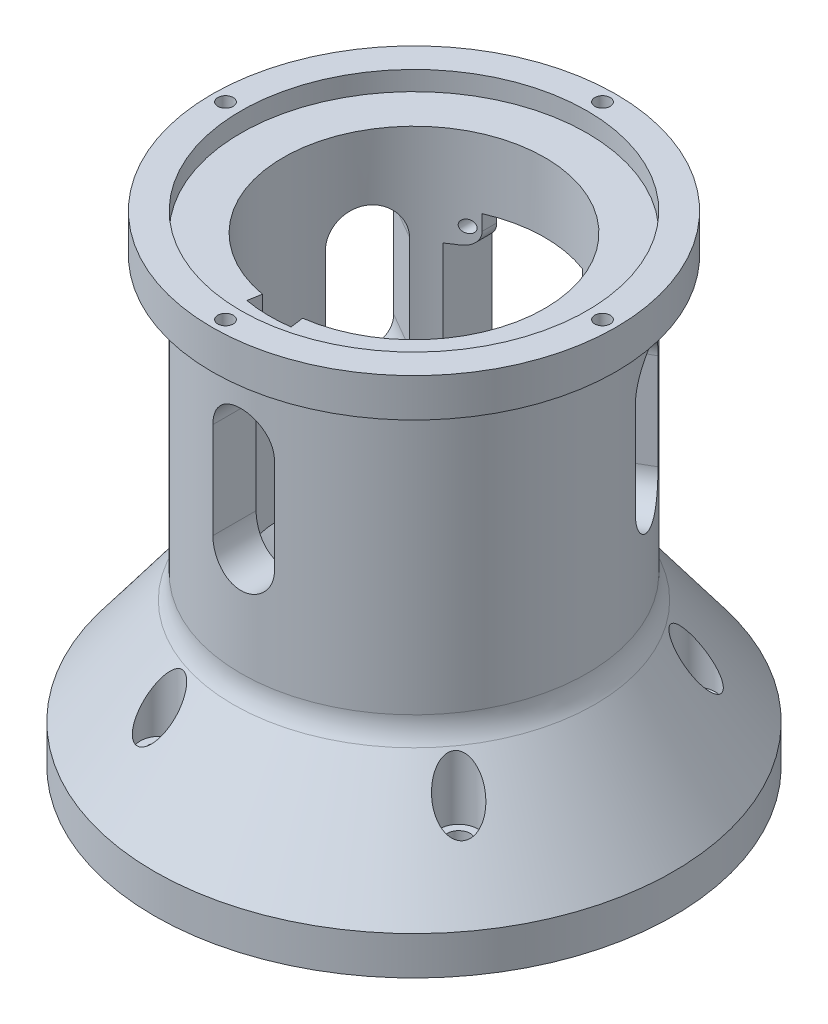
SolidWorks part; units mm, degrees
ref_plane "Front Plane" through (0, 0, 0) normal (0, 0, 1) x (1, 0, 0)
ref_plane "Top Plane" through (0, 0, 0) normal (0, 1, 0) x (1, 0, 0)
ref_plane "Right Plane" through (0, 0, 0) normal (1, 0, 0) x (0, 0, -1)
sketch "Sketch1" plane through (0, 0, 0) normal (0, 1, 0) x (1, 0, 0)
  circle A0 centre (0, 0) radius 67.5
  dimension "D1" = 135
ref_plane "Plane1" through (0, 30, 0) normal (0, 1, 0) x (1, 0, 0)
sketch "Sketch2" plane through (0, 30, 0) normal (0, 1, 0) x (1, 0, 0)
  circle A0 centre (0, 0) radius 45
  dimension "D1" = 90
loft "Loft1" add profiles "Sketch1", "Sketch2" connector at (0, 0, 67.5) connector at (0, 30, 45)
sketch "Sketch4" plane through (0, 30, 0) normal (0, 1, 0) x (1, 0, 0)
  circle A0 centre (0, 0) radius 52.5 construction
  circle A1 centre (-52.5, 0) radius 3
  circle A2 centre (-16.2234, 49.9305) radius 3
  circle A3 centre (42.4734, 30.8587) radius 3
  circle A4 centre (42.4734, -30.8587) radius 3
  circle A5 centre (-16.2234, -49.9305) radius 3
  point P15 (0, 0)
  dimension "D1" = 105
  dimension "D2" = 6
  dimension "D3" = 5
extrude "Cut-Extrude2" cut sketch "Sketch4" against normal through all
sketch "Sketch5" plane through (0, 30, 0) normal (0, 1, 0) x (1, 0, 0)
  circle A0 centre (-52.5, 0) radius 3 construction
  circle A1 centre (-52.5, 0) radius 3
  circle A2 centre (-52.5, 0) radius 5
  circle A3 centre (-16.2234, 49.9305) radius 5
  circle A4 centre (42.4734, 30.8587) radius 5
  circle A5 centre (42.4734, -30.8587) radius 5
  circle A6 centre (-16.2234, -49.9305) radius 5
  point P14 (0, 0)
  dimension "D1" = 10
  dimension "D3" = 52.5
  dimension "D2" = 5
extrude "Cut-Extrude3" cut sketch "Sketch5" against normal blind 20
sketch "Sketch6" plane through (0, 30, 0) normal (0, 1, 0) x (1, 0, 0)
  circle A1 centre (0, 0) radius 45
  circle A2 centre (0, 0) radius 45
  dimension "D1" = 0
extrude "Boss-Extrude1" add sketch "Sketch6" along normal blind 80
fillet "Fillet1" radius 10 1 edges at (0, 30, 45)
sketch "Sketch11" plane through (17.444, 57.5446, 0) normal (0, 0, 1) x (1, 0, 0)
  line L0 (-17.444, 52.4554) -> (-51.444, 52.4554)
  line L1 (27.556, 52.4554) -> (-62.444, 52.4554) construction
  line L2 (-51.444, 52.4554) -> (-51.444, -28.5446)
  line L5 (-51.444, -28.5446) -> (-40.444, -38.7852)
  line L8 (-40.444, -38.7852) -> (-17.444, -38.7852)
  line L9 (-17.444, 52.4554) -> (-17.444, -38.7852)
  dimension "D1" = 34
  dimension "D2" = 137.047
  dimension "D3" = 23
  dimension "D4" = 81
revolve "Cut-Revolve1" cut sketch "Sketch11" angle 360 about L9
sketch "Sketch12" plane through (0, 0, 0) normal (0, -1, 0) x (1, 0, 0)
  circle A1 centre (0, 0) radius 67.5
  circle A2 centre (0, 0) radius 67.5
  dimension "D1" = 0
extrude "Boss-Extrude2" add sketch "Sketch12" along normal blind 10
sketch "Sketch15" plane through (0, -10, 0) normal (0, -1, 0) x (1, 0, 0)
  circle A0 centre (42.4734, 30.8587) radius 3 construction
  circle A3 centre (-52.5, 0) radius 3
  circle A4 centre (-52.5, 0) radius 3
  circle A5 centre (42.4734, -30.8587) radius 3 construction
  circle A6 centre (-16.2234, -49.9305) radius 3 construction
  circle A7 centre (-16.2234, 49.9305) radius 3 construction
  circle A8 centre (42.4734, 30.8587) radius 3
  circle A9 centre (42.4734, -30.8587) radius 3
  circle A10 centre (-16.2234, -49.9305) radius 3
  circle A11 centre (-16.2234, 49.9305) radius 3
  dimension "D2" = 0
extrude "Cut-Extrude5" cut sketch "Sketch15" against normal blind 20
sketch "Sketch16" plane through (0, 0, 0) normal (0, 0, 1) x (1, 0, 0)
  line L0 (0, 85) -> (0, 60) construction
  line L1 (8, 85) -> (8, 60)
  line L2 (-8, 85) -> (-8, 60)
  arc A0 (8, 85) -> (-8, 85) centre (0, 85) ccw
  arc A1 (-8, 60) -> (8, 60) centre (0, 60) ccw
  point P3 (0, 72.5)
  dimension "D3" = 8
  dimension "D1" = 60
  dimension "D2" = 25
extrude "Cut-Extrude6" cut sketch "Sketch16" along normal blind 50
pattern_circular "CirPattern1" count 3 every 120 about axis through (0, 110, 0) along (0, 1, 0) of "Cut-Extrude6"
sketch "Sketch18" plane through (0, 0, 0) normal (0, 0, 1) x (1, 0, 0)
  line L0 (0, 0) -> (0, 72.5) construction
  line L1 (16, 85.5) -> (20, 85.5)
  line L2 (12, 92) -> (-13.5, 92)
  line L3 (20, 85.5) -> (20, 60)
  line L4 (13.5, 52) -> (-12, 52)
  line L5 (-20, 84) -> (-20, 58.5)
  line L6 (13.7161, 86.2161) -> (-14.3542, 58.1458) construction
  line L8 (12, 89.5) -> (12, 92)
  line L9 (13.5, 56) -> (13.5, 52)
  line L10 (17.5, 60) -> (20, 60)
  line L11 (-16, 58.5) -> (-20, 58.5)
  line L12 (-12, 54.5) -> (-12, 52)
  line L13 (-13.5, 88) -> (-13.5, 92)
  line L14 (-17.5, 84) -> (-20, 84)
  line L17 (13.6021, 56.8979) -> (-14.6716, 85.1716) construction
  arc A5 (12, 89.5) -> (16, 85.5) centre (16, 89.5) ccw
  arc A6 (17.5, 60) -> (13.5, 56) centre (17.5, 56) ccw
  arc A7 (-12, 54.5) -> (-16, 58.5) centre (-16, 54.5) ccw
  arc A8 (-17.5, 84) -> (-13.5, 88) centre (-17.5, 88) ccw
  point P39 (0, 72)
  dimension "D4" = 4
  dimension "D3" = 40
  dimension "D1" = 72.5
  dimension "D2" = 4
extrude "Cut-Extrude7" cut sketch "Sketch18" against normal blind 50
ref_plane "Plane2" through (0, 0, -60) normal (0, 0, 1) x (1, 0, 0)
sketch "Sketch22" plane through (0, 0, -60) normal (0, 0, 1) x (1, 0, 0)
  line L0 (0, 0) -> (0, 72.5) construction
  line L1 (-67.5, 0) -> (67.5, 0) construction
  line L3 (20, 92.5) -> (-20, 92.5)
  line L4 (20, 92.5) -> (20, 52.5)
  line L5 (20, 52.5) -> (-20, 52.5)
  line L6 (-20, 92.5) -> (-20, 52.5)
  line L7 (20, 92.5) -> (-20, 52.5) construction
  line L8 (20, 52.5) -> (-20, 92.5) construction
  dimension "D1" = 72.5
  dimension "D2" = 40
  dimension "D3" = 40
extrude "Cut-Extrude8" cut sketch "Sketch22" along normal blind 25
sketch "Sketch23" plane through (0, 0, -60) normal (0, 0, 1) x (1, 0, 0)
  line L0 (0, 0) -> (0, 72.5) construction
  line L1 (0, 72.5) -> (-5.5729, 72.5) construction
  line L2 (20, 92.5) -> (-20, 92.5) construction
  line L3 (20, 92.5) -> (20, 52.5) construction
  line L4 (20, 52.5) -> (-20, 52.5) construction
  line L5 (-20, 92.5) -> (-20, 52.5) construction
  circle A0 centre (16, 88.5) radius 1.6
  circle A4 centre (-16, 88.5) radius 1.6
  circle A5 centre (-16, 56.5) radius 1.6
  circle A6 centre (16, 56.5) radius 1.6
  dimension "D3" = 3.2
  dimension "D5" = 16
  dimension "D1" = 72.5
  dimension "D2" = 40
  dimension "D4" = 16
extrude "Cut-Extrude9" cut sketch "Sketch23" along normal blind 36
sketch "Sketch30" plane through (0, 0, 0) normal (0, 0, 1) x (1, 0, 0)
  line L0 (-3.5, 102) -> (3.5, 102) construction
  line L1 (-3.5, 104) -> (3.5, 104)
  line L2 (-3.5, 100) -> (3.5, 100)
  arc A0 (-3.5, 104) -> (-3.5, 100) centre (-3.5, 102) ccw
  arc A1 (3.5, 100) -> (3.5, 104) centre (3.5, 102) ccw
  point P2 (0, 102)
  dimension "D3" = 2
  dimension "D1" = 102
  dimension "D2" = 7
extrude "Cut-Extrude12" cut sketch "Sketch30" along normal blind 70
sketch "Sketch32" plane through (0, 110, 0) normal (0, 1, 0) x (1, 0, 0)
  line L0 (4.7093, -33.6723) -> (5.1941, -37.1385)
  line L1 (-5.9265, -33.4795) -> (-6.5365, -36.9259)
  circle A0 centre (0, 0) radius 34 construction
  arc A1 (-5.9265, -33.4795) -> (4.7093, -33.6723) centre (0, 0) ccw
  arc A2 (-6.5365, -36.9259) -> (5.1941, -37.1385) centre (0, 0) ccw
  dimension "D1" = 75
  dimension "D2" = 18
extrude "Cut-Extrude14" cut sketch "Sketch32" against normal up to surface (6 mm away) up to face at (0, 104, 39.4208)
sketch "Sketch33" plane through (0, 110, 0) normal (0, 1, 0) x (1, 0, 0)
  circle A0 centre (0, 0) radius 52.5
  circle A1 centre (0, 0) radius 45 construction
  circle A2 centre (0, 0) radius 45
  dimension "D1" = 105
extrude "Boss-Extrude3" add sketch "Sketch33" against normal mid plane 10
sketch "Sketch34" plane through (0, 115, 0) normal (0, 1, 0) x (1, 0, 0)
  circle A0 centre (0, 0) radius 49 construction
  circle A1 centre (0, 49) radius 2
  circle A2 centre (49, 0) radius 2
  circle A3 centre (0, -49) radius 2
  circle A4 centre (-49, 0) radius 2
  point P14 (0, 0)
  dimension "D1" = 98
  dimension "D2" = 4
extrude "Cut-Extrude15" cut sketch "Sketch34" against normal blind 10
